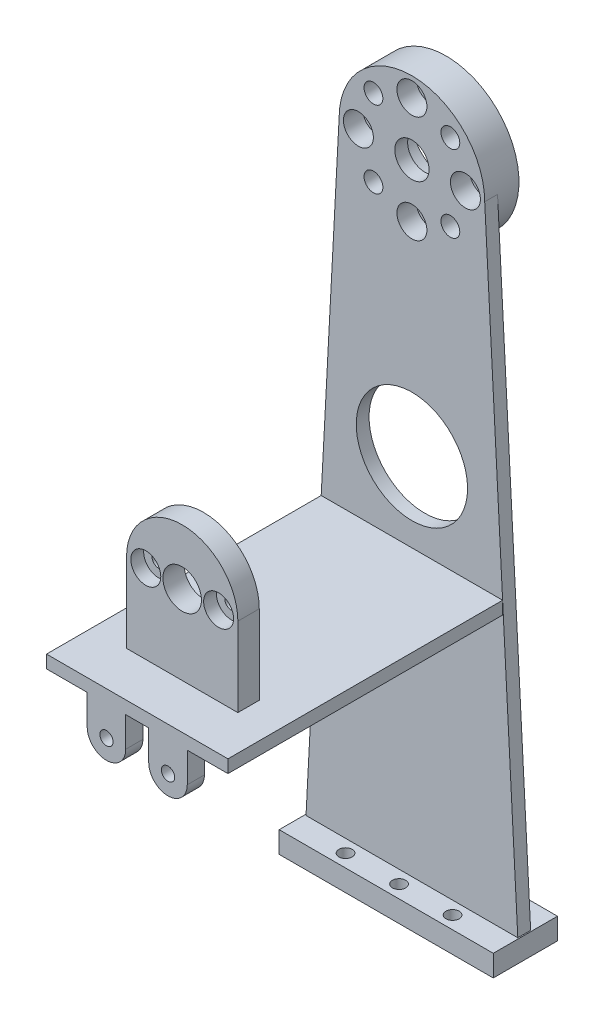
SolidWorks part; units mm, degrees
ref_plane "Front Plane" through (0, 0, 0) normal (0, 0, 1) x (1, 0, 0)
ref_plane "Top Plane" through (0, 0, 0) normal (0, 1, 0) x (1, 0, 0)
ref_plane "Right Plane" through (0, 0, 0) normal (1, 0, 0) x (0, 0, -1)
sketch "Sketch1" plane through (0, 0, 0) normal (0, 0, 1) x (1, 0, 0)
  line L0 (-25, 0) -> (25, 0)
  line L1 (0, 0) -> (0, 150) construction
  line L2 (-17, 150) -> (-25, 0)
  line L3 (25, 0) -> (17, 150)
  line L4 (0, 150) -> (0, 90) construction
  circle A0 centre (0, 150) radius 4
  arc A1 (-17, 150) -> (17, 150) centre (0, 150) cw
  circle A2 centre (0, 90) radius 13
  point P4 (0, 0)
extrude "Boss-Extrude1" add sketch "Sketch1" along normal blind 3
sketch "Sketch2" plane through (0, 0, 0) normal (0, 0, -1) x (-1, 0, 0)
  circle A0 centre (0, 150) radius 17
  circle A1 centre (0, 150) radius 8
extrude "Boss-Extrude2" add sketch "Sketch2" along normal blind 5
sketch "Sketch3" plane through (0, 0, 3) normal (0, 0, 1) x (1, 0, 0)
  line L0 (0, 150) -> (8.9803, 158.9803) construction
  circle A0 centre (0, 150) radius 12.5 construction
  circle A1 centre (-12.5, 150) radius 1.55
  circle A2 centre (0, 162.5) radius 1.55
  circle A3 centre (12.5, 150) radius 1.55
  circle A4 centre (0, 137.5) radius 1.55
  circle A5 centre (0, 150) radius 12.7 construction
  circle A6 centre (8.9803, 158.9803) radius 1
  circle A7 centre (8.9803, 141.0197) radius 1
  circle A8 centre (-8.9803, 141.0197) radius 1
  circle A9 centre (-8.9803, 158.9803) radius 1
  point P14 (0, 150)
  point P24 (0, 150)
  dimension "D1" = 4
  dimension "D2" = 4
extrude "Cut-Extrude1" cut sketch "Sketch3" against normal blind 8
sketch "Sketch4" plane through (0, 0, 3) normal (0, 0, 1) x (1, 0, 0)
  circle A0 centre (-12.5, 150) radius 3.5
  circle A1 centre (0, 162.5) radius 3.5
  circle A2 centre (12.5, 150) radius 3.5
  circle A3 centre (0, 137.5) radius 3.5
  circle A4 centre (-8.9803, 158.9803) radius 2.2
  circle A5 centre (8.9803, 158.9803) radius 2.2
  circle A6 centre (8.9803, 141.0197) radius 2.2
  circle A7 centre (-8.9803, 141.0197) radius 2.2
  point P12 (0, 150)
  point P22 (0, 150)
  dimension "D1" = 4
  dimension "D2" = 4
extrude "Cut-Extrude2" cut sketch "Sketch4" against normal blind 4.5
sketch "Sketch5" plane through (0, 0, 0) normal (0, -1, 0) x (1, 0, 0)
  line L3 (-25, -6) -> (-25, 9)
  line L5 (25, -6) -> (25, 9)
  line L7 (-25, 9) -> (25, 9)
  line L8 (25, -6) -> (-25, -6)
  circle A0 centre (-12.5, 6) radius 1.55
  circle A1 centre (0, 6) radius 1.55
  circle A2 centre (12.5, 6) radius 1.55
  circle A3 centre (0, -3) radius 1.55
  circle A4 centre (-12.5, -3) radius 1.55
  circle A5 centre (12.5, -3) radius 1.55
extrude "Boss-Extrude3" add sketch "Sketch5" against normal blind 5
sketch "Sketch8" plane through (0, 0, 3) normal (0, 0, 1) x (1, 0, 0)
  line L0 (-21.1867, 71.5) -> (21.1867, 71.5) construction
  line L2 (25, 0) -> (17, 150) construction
  point P3 (0, 71.5)
ref_plane "Plane3" through (0, 71.5, 0) normal (0, -1, 0) x (1, 0, 0)
sketch "Sketch9" plane through (0, 71.5, 0) normal (0, -1, 0) x (1, 0, 0)
  line L0 (-21.1867, 3) -> (21.1867, 3)
  line L1 (-21.1867, 3) -> (21.1867, 3) construction
  line L2 (21.1867, 3) -> (21.1867, 67.15)
  line L3 (21.1867, 67.15) -> (-21.1867, 67.15)
  line L4 (-21.1867, 67.15) -> (-21.1867, 3)
extrude "Boss-Extrude6" add sketch "Sketch9" along normal blind 3
sketch "Sketch10" plane through (0, 71.5, 0) normal (0, 1, 0) x (1, 0, 0)
  line L0 (0, -67.15) -> (0, -51.65) construction
  line L1 (21.1867, -67.15) -> (-21.1867, -67.15) construction
  line L2 (-21.1867, -51.65) -> (21.1867, -51.65) construction
  line L3 (21.1867, -3) -> (21.1867, -67.15) construction
  point P10 (0, -51.65)
ref_plane "Plane4" through (0, 0, 51.65) normal (0, 0, 1) x (1, 0, 0)
sketch "Sketch11" plane through (0, 0, 51.65) normal (0, 0, 1) x (1, 0, 0)
  line L0 (-8.5, 90) -> (8.5, 90) construction
  line L2 (-13, 90) -> (-13, 71.5)
  line L3 (-21.1867, 71.5) -> (21.1867, 71.5) construction
  line L4 (-13, 71.5) -> (13, 71.5)
  line L5 (13, 71.5) -> (13, 90)
  circle A0 centre (-8.5, 90) radius 1.55
  circle A1 centre (8.5, 90) radius 1.55
  arc A2 (-13, 90) -> (13, 90) centre (0, 90) cw
  circle A3 centre (0, 90) radius 13 construction
  circle A4 centre (0, 90) radius 4.5
  point P4 (0, 90)
extrude "Boss-Extrude7" add sketch "Sketch11" along normal blind 5
sketch "Sketch12" plane through (0, 0, 67.15) normal (0, 0, 1) x (1, 0, 0)
  line L0 (-21.1867, 68.5) -> (-7.1867, 68.5) construction
  line L1 (-21.1867, 68.5) -> (21.1867, 68.5) construction
  line L2 (21.1867, 68.5) -> (7.1867, 68.5) construction
  line L3 (-7.1867, 68.5) -> (-7.1867, 61.5) construction
  line L4 (7.1867, 68.5) -> (7.1867, 61.5) construction
  line L11 (-11.6867, 61.5) -> (-11.6867, 68.5)
  line L12 (-11.6867, 68.5) -> (-2.6867, 68.5)
  line L13 (21.1867, 68.5) -> (-21.1867, 68.5) construction
  line L14 (-2.6867, 68.5) -> (-2.6867, 61.5)
  line L15 (2.6867, 61.5) -> (2.6867, 68.5)
  line L16 (2.6867, 68.5) -> (11.6867, 68.5)
  line L17 (11.6867, 68.5) -> (11.6867, 61.5)
  arc A0 (-11.6867, 61.5) -> (-2.6867, 61.5) centre (-7.1867, 61.5) ccw
  arc A1 (2.6867, 61.5) -> (11.6867, 61.5) centre (7.1867, 61.5) ccw
  circle A2 centre (-7.1867, 61.5) radius 1.55
  circle A3 centre (7.1867, 61.5) radius 1.55
extrude "Boss-Extrude8" add sketch "Sketch12" against normal blind 4
sketch "Sketch13" plane through (0, 0, 56.65) normal (0, 0, 1) x (1, 0, 0)
  circle A0 centre (-8.5, 90) radius 3.5
  circle A1 centre (8.5, 90) radius 3.5
extrude "Cut-Extrude3" cut sketch "Sketch13" against normal blind 3
